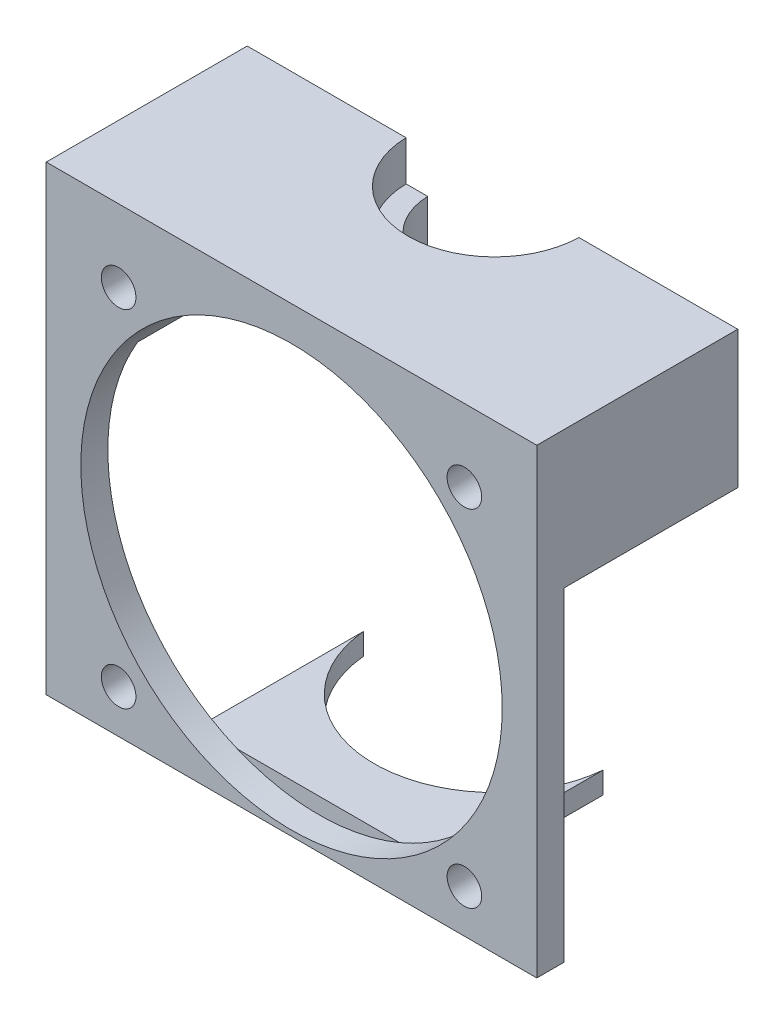
SolidWorks part; units mm, degrees
ref_plane "Front Plane" through (0, 0, 0) normal (0, 0, 1) x (1, 0, 0)
ref_plane "Top Plane" through (0, 0, 0) normal (0, 1, 0) x (1, 0, 0)
ref_plane "Right Plane" through (0, 0, 0) normal (1, 0, 0) x (0, 0, -1)
sketch "Sketch1" plane through (0, 0, 0) normal (0, 0, 1) x (1, 0, 0)
  line L1 (0, 0) -> (45.4, 0)
  line L2 (0, 0) -> (0, 12.7)
  line L3 (0, 12.7) -> (45.4, 12.7)
  line L4 (45.4, 0) -> (45.4, 12.7)
  line L5 (0, 0) -> (45.4, 12.7) construction
  line L6 (0, 12.7) -> (45.4, 0) construction
  point P4 (22.7, 6.35)
  dimension "D1" = 45.4
  dimension "D2" = 12.7
extrude "Boss-Extrude1" add sketch "Sketch1" along normal blind 18.8
ref_plane "Plane1" through (0, 3, 0) normal (0, 1, 0) x (1, 0, 0)
sketch "Sketch3" plane through (0, 0, 0) normal (0, 1, 0) x (1, 0, 0)
  line L0 (0, 0) -> (45.4, 0) construction
  circle A0 centre (22.7, 0) radius 7.5
  point P4 (21, 0)
  dimension "D1" = 15
extrude "Cut-Extrude2" cut sketch "Sketch3" along normal blind 3
sketch "Sketch2" plane through (0, 3, 0) normal (0, 1, 0) x (1, 0, 0)
  line L0 (45.4, 0) -> (0, 0) construction
  line L1 (15.2, 0) -> (30.2, 0) construction
  circle A0 centre (22.7, 0) radius 6
  point P4 (21, 0)
  dimension "D1" = 12
extrude "Cut-Extrude1" cut sketch "Sketch2" along normal blind 6
sketch "Sketch4" plane through (0, 12.7, 0) normal (0, 1, 0) x (1, 0, 0)
  line L0 (45.4, 0) -> (0, 0) construction
  line L1 (16.7, 0) -> (28.7, 0) construction
  circle A0 centre (22.7, 0) radius 8
  point P4 (21, 0)
  dimension "D1" = 16
extrude "Cut-Extrude3" cut sketch "Sketch4" against normal blind 3.7
sketch "Sketch5" plane through (0, 0, 0) normal (0, 1, 0) x (1, 0, 0)
  line L0 (45.4, -18.8) -> (45.4, 0) construction
  line L1 (0, 0) -> (45.4, 0)
  line L2 (0, 0) -> (0, -0.2)
  line L3 (0, -0.2) -> (45.4, -0.2)
  line L4 (45.4, 0) -> (45.4, -0.2)
  line L5 (0, 0) -> (45.4, -0.2) construction
  line L6 (0, -0.2) -> (45.4, 0) construction
  point P4 (22.7, -0.1)
  dimension "D1" = 0.2
extrude "Cut-Extrude5" cut sketch "Sketch5" against normal through all and the other way through all
sketch "Sketch6" plane through (0, 0, 0.2) normal (0, 0, -1) x (-1, 0, 0)
  circle A0 centre (-38.7, 6) radius 1.6
  circle A1 centre (-6.7, 6) radius 1.6
  point P4 (-38.4, 6.7)
  point P5 (-7, 6.7)
  point P6 (-38.7, 6)
  point P7 (-6.7, 6)
  dimension "D1" = 3.2
  dimension "D2" = 3.2
extrude "Cut-Extrude6" cut sketch "Sketch6" against normal through all
sketch "Sketch7" plane through (0, 0, 18.8) normal (0, 0, 1) x (1, 0, 0)
  line L1 (0, 0) -> (45.4, 0)
  line L2 (0, 0) -> (0, -30)
  line L3 (0, -30) -> (45.4, -30)
  line L4 (45.4, 0) -> (45.4, -30)
  line L5 (0, 0) -> (45.4, -30) construction
  line L6 (0, -30) -> (45.4, 0) construction
  point P4 (22.7, -15)
  point P5 (0, 0)
  point P7 (45.4, 0)
  dimension "D1" = 30
extrude "Boss-Extrude2" add sketch "Sketch7" against normal blind 2.5
sketch "Sketch8" plane through (0, 0, 18.8) normal (0, 0, 1) x (1, 0, 0)
  circle A0 centre (22.7, -10) radius 19.5
  dimension "D1" = 39
extrude "Cut-Extrude7" cut sketch "Sketch8" against normal up to surface (2.5 mm away) up to face at (22.7, -15, 16.3)
ref_plane "Plane2" through (14.9526, -41.0819, 0) normal (0.342, -0.9397, 0) x (0, 0, 1)
ref_plane "Plane3" through (-9.6418, -26.4907, 0) normal (-0.342, -0.9397, 0) x (0, 0, 1)
fillet "Fillet1" radius 16 1 edges at (22.7, 0, 16.3)
sketch "Sketch9" plane through (0, 0, 18.8) normal (0, 0, 1) x (1, 0, 0)
  circle A0 centre (6.7, -26) radius 1.6
  circle A1 centre (38.7, -26) radius 1.6
  dimension "D1" = 3.2
  dimension "D2" = 3.2
extrude "Cut-Extrude8" cut sketch "Sketch9" against normal blind 4
sketch "Sketch10" plane through (0, 0, 16.3) normal (0, 0, -1) x (-1, 0, 0)
  line L0 (0, -30) -> (-45.4, -30) construction
  line L1 (-33.8, -30) -> (-11.6, -30)
  line L2 (-33.8, -30) -> (-33.8, -28)
  line L3 (-33.8, -28) -> (-11.6, -28)
  line L4 (-11.6, -30) -> (-11.6, -28)
  line L5 (-33.8, -30) -> (-11.6, -28) construction
  line L6 (-33.8, -28) -> (-11.6, -30) construction
  line L7 (-45.4, -30) -> (-45.4, 0) construction
  line L8 (0, 0) -> (0, -30) construction
  point P4 (-22.7, -29)
  dimension "D1" = 11.6
  dimension "D2" = 11.6
  dimension "D3" = 2
extrude "Boss-Extrude3" add sketch "Sketch10" along normal blind 16
sketch "Sketch11" plane through (0, -30, 0) normal (0, -1, 0) x (1, 0, 0)
  circle A1 centre (22.7, 0) radius 11.15
  dimension "D1" = 22.3
extrude "Cut-Extrude9" cut sketch "Sketch11" against normal blind 18
